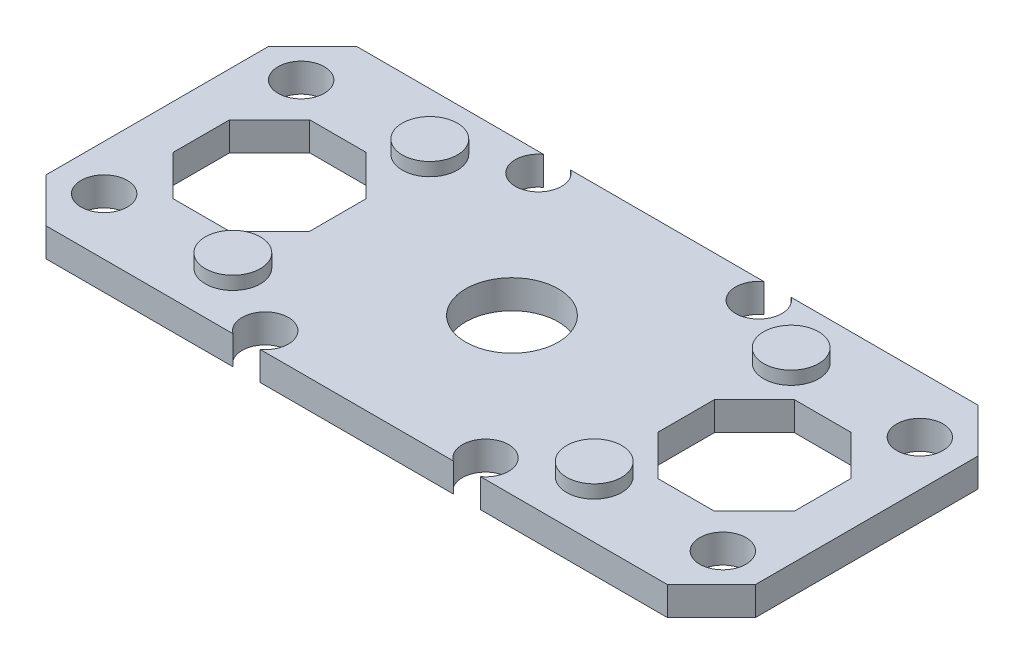
SolidWorks part; units mm, degrees
ref_plane "Front" through (0, 0, 0) normal (0, 0, 1) x (1, 0, 0)
ref_plane "Top" through (0, 0, 0) normal (0, 1, 0) x (1, 0, 0)
ref_plane "Right" through (0, 0, 0) normal (1, 0, 0) x (0, 0, -1)
sketch "Sketch1" plane through (0, 0, 0) normal (0, 1, 0) x (1, 0, 0)
  line L0 (-5.5671, 8.9535) -> (5.5671, 8.9535)
  line L1 (-6.35, -7.874) -> (6.35, -7.874) construction
  line L2 (-6.35, -7.874) -> (-6.35, 7.874) construction
  line L3 (-6.35, 7.874) -> (6.35, 7.874) construction
  line L4 (6.35, -7.874) -> (6.35, 7.874) construction
  line L5 (-6.35, -7.874) -> (6.35, 7.874) construction
  line L6 (-6.35, 7.874) -> (6.35, -7.874) construction
  line L7 (-17.8308, -5.6769) -> (17.8308, -5.6769) construction
  line L8 (-17.8308, -5.6769) -> (-17.8308, 5.6769) construction
  line L9 (-17.8308, 5.6769) -> (17.8308, 5.6769) construction
  line L10 (17.8308, -5.6769) -> (17.8308, 5.6769) construction
  line L11 (-17.8308, -5.6769) -> (17.8308, 5.6769) construction
  line L12 (-17.8308, 5.6769) -> (17.8308, -5.6769) construction
  line L13 (-10.414, -5.6769) -> (10.414, -5.6769) construction
  line L14 (-10.414, -5.6769) -> (-10.414, 5.6769) construction
  line L15 (-10.414, 5.6769) -> (10.414, 5.6769) construction
  line L16 (10.414, -5.6769) -> (10.414, 5.6769) construction
  line L17 (-10.414, -5.6769) -> (10.414, 5.6769) construction
  line L18 (-10.414, 5.6769) -> (10.414, -5.6769) construction
  line L19 (-20.447, -8.9535) -> (-7.1329, -8.9535)
  line L20 (-20.447, -8.9535) -> (-20.447, 8.9535)
  line L21 (-20.447, 8.9535) -> (-7.1329, 8.9535)
  line L22 (20.447, -8.9535) -> (20.447, 8.9535)
  line L23 (-20.447, -8.9535) -> (20.447, 8.9535) construction
  line L24 (-20.447, 8.9535) -> (20.447, -8.9535) construction
  line L25 (7.1329, 8.9535) -> (20.447, 8.9535)
  line L26 (7.1329, -8.9535) -> (20.447, -8.9535)
  line L27 (-5.5671, -8.9535) -> (5.5671, -8.9535)
  circle A0 centre (-17.8308, 5.6769) radius 1.3335
  arc A1 (-7.1329, 8.9535) -> (-5.5671, 8.9535) centre (-6.35, 7.874) ccw
  arc A2 (5.5671, 8.9535) -> (7.1329, 8.9535) centre (6.35, 7.874) ccw
  circle A3 centre (17.8308, 5.6769) radius 1.3335
  circle A4 centre (17.8308, -5.6769) radius 1.3335
  arc A5 (7.1329, -8.9535) -> (5.5671, -8.9535) centre (6.35, -7.874) ccw
  arc A6 (-5.5671, -8.9535) -> (-7.1329, -8.9535) centre (-6.35, -7.874) ccw
  circle A7 centre (-17.8308, -5.6769) radius 1.3335
  circle A8 centre (-10.414, 5.6769) radius 1.5875
  circle A9 centre (10.414, 5.6769) radius 1.5875
  circle A10 centre (10.414, -5.6769) radius 1.5875
  circle A11 centre (-10.414, -5.6769) radius 1.5875
  point P0 (0, 0)
  point P6 (0, 0)
  point P11 (0, 0)
  point P16 (0, 0)
  dimension "D8" = 2.667
  dimension "D9" = 3.175
  dimension "D1" = 12.7
  dimension "D2" = 15.748
  dimension "D3" = 11.3538
  dimension "D4" = 35.6616
  dimension "D5" = 40.894
  dimension "D6" = 17.907
  dimension "D7" = 20.828
extrude "Boss-Extrude1" add sketch "Sketch1" along normal blind 1.651
chamfer "Chamfer1" distance 2.54 angle 45 4 edges at (-20.447, 0.8255, 8.9535) (-20.447, 0.8255, -8.9535) (20.447, 0.8255, -8.9535) (20.447, 0.8255, 8.9535)
extrude "Boss-Extrude2" add sketch "Sketch1<2>" along normal blind 2.413 contours A8 | A9 | A10 | A11
sketch "Sketch1<2>" plane through (0, 0, 0) normal (0, 1, 0) x (1, 0, 0) same geometry as "Sketch1"
extrude "Cut-Extrude1" cut sketch "Sketch1<3>" along normal blind 0.889 contours A11 | A10 | A9 | A8
sketch "Sketch1<3>" plane through (0, 0, 0) normal (0, 1, 0) x (1, 0, 0) same geometry as "Sketch1"
sketch "Sketch3" plane through (0, 1.651, 0) normal (0, 1, 0) x (1, 0, 0)
  line L1 (-17.907, -3.937) -> (17.907, -3.937) construction
  line L2 (-17.907, -3.937) -> (-17.907, 3.937) construction
  line L3 (-17.907, 3.937) -> (17.907, 3.937) construction
  line L4 (17.907, -3.937) -> (17.907, 3.937) construction
  line L5 (-17.907, -3.937) -> (17.907, 3.937) construction
  line L6 (-17.907, 3.937) -> (17.907, -3.937) construction
  line L7 (-10.033, 1.6308) -> (-12.3392, 3.937)
  line L8 (-12.3392, 3.937) -> (-15.6008, 3.937)
  line L9 (-15.6008, 3.937) -> (-17.907, 1.6308)
  line L10 (-17.907, 1.6308) -> (-17.907, -1.6308)
  line L11 (-17.907, -1.6308) -> (-15.6008, -3.937)
  line L12 (-15.6008, -3.937) -> (-12.3392, -3.937)
  line L13 (-12.3392, -3.937) -> (-10.033, -1.6308)
  line L14 (-10.033, -1.6308) -> (-10.033, 1.6308)
  line L15 (17.907, 1.6308) -> (15.6008, 3.937)
  line L16 (15.6008, 3.937) -> (12.3392, 3.937)
  line L17 (12.3392, 3.937) -> (10.033, 1.6308)
  line L18 (10.033, 1.6308) -> (10.033, -1.6308)
  line L19 (10.033, -1.6308) -> (12.3392, -3.937)
  line L20 (12.3392, -3.937) -> (15.6008, -3.937)
  line L21 (15.6008, -3.937) -> (17.907, -1.6308)
  line L22 (17.907, -1.6308) -> (17.907, 1.6308)
  circle A0 centre (-13.97, 0) radius 3.937 construction
  circle A1 centre (13.97, 0) radius 3.937 construction
  circle A2 centre (0, 0) radius 2.667
  point P0 (0, 0)
  dimension "D3" = 5.334
  dimension "D1" = 7.874
  dimension "D2" = 35.814
extrude "Cut-Extrude3" cut sketch "Sketch3" against normal through all
